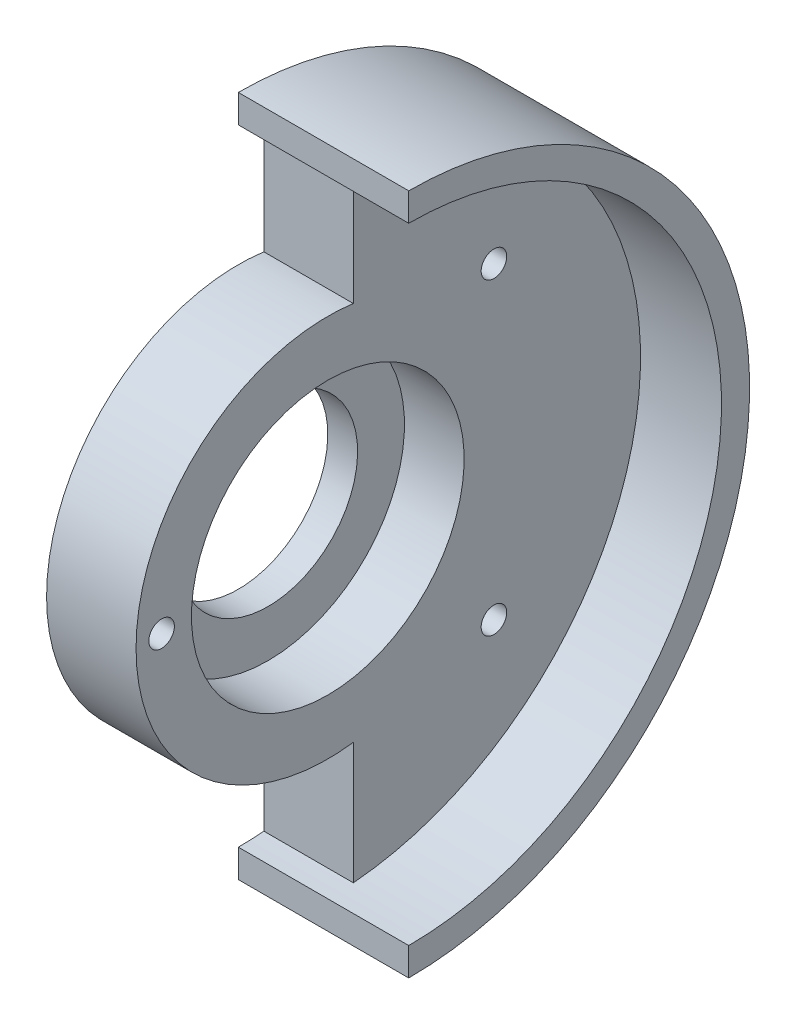
SolidWorks part; units mm, degrees
ref_plane "Front Plane" through (0, 0, 0) normal (0, 0, 1) x (1, 0, 0)
ref_plane "Top Plane" through (0, 0, 0) normal (0, 1, 0) x (1, 0, 0)
ref_plane "Right Plane" through (0, 0, 0) normal (1, 0, 0) x (0, 0, -1)
sketch "Sketch1" plane through (0, 0, 0) normal (0, 0, 1) x (1, 0, 0)
  line L0 (20, 40) -> (20, 36.7)
  line L1 (20, 36.7) -> (10.5, 36.7)
  line L2 (10.5, 36.7) -> (10.5, 16)
  line L3 (10.5, 16) -> (3.5, 16)
  line L4 (3.5, 16) -> (3.5, 10.5)
  line L5 (3.5, 10.5) -> (0, 10.5)
  line L6 (0, 10.5) -> (0, 40)
  line L7 (0, 40) -> (20, 40)
  line L8 (20, 0) -> (0, 0) construction
  dimension "D1" = 20
  dimension "D2" = 7
  dimension "D3" = 9.5
  dimension "D4" = 10.5
  dimension "D5" = 16
  dimension "D6" = 36.7
  dimension "D7" = 40
revolve "Revolve1" add sketch "Sketch1" angle 360 about L8
sketch "Sketch2" plane through (10.5, 0, 0) normal (1, 0, 0) x (0, 0, -1)
  line L0 (3, 22.2991) -> (3, 36.5772)
  line L1 (3, -22.2991) -> (3, -36.5772)
  line L2 (0, 40) -> (0, 36.7)
  line L3 (0, -36.7) -> (0, -40)
  arc A0 (3, 36.5772) -> (0, 36.7) centre (0, 0) ccw
  arc A1 (3, 22.2991) -> (3, -22.2991) centre (0, 0) ccw
  circle A2 centre (-19.5, 0) radius 1.5
  circle A3 centre (0, 0) radius 36.7 construction
  arc A4 (3, 22.2991) -> (3, -22.2991) centre (0, 0) ccw construction
  circle A5 centre (19.5, -18.0917) radius 1.5
  circle A6 centre (19.5, 18.0917) radius 1.5
  circle A7 centre (19.5, 18.0917) radius 1.5 construction
  circle A8 centre (-19.5, 0) radius 1.5 construction
  circle A9 centre (19.5, -18.0917) radius 1.5 construction
  arc A10 (0, 40) -> (0, -40) centre (0, 0) ccw
  circle A11 centre (0, 0) radius 40 construction
  arc A12 (0, -36.7) -> (3, -36.5772) centre (0, 0) ccw
extrude "Cut-Extrude1" cut sketch "Sketch2" against normal through all both and the other way through all
sketch "Sketch3" plane through (0, 0, 0) normal (-1, 0, 0) x (0, 0, 1)
  circle A0 centre (-19.5, 18.0917) radius 2.75
  circle A1 centre (19.5, 0) radius 2.75
  circle A2 centre (-19.5, -18.0917) radius 2.75
  dimension "D1" = 5.5
extrude "Cut-Extrude2" cut sketch "Sketch3" against normal blind 5
